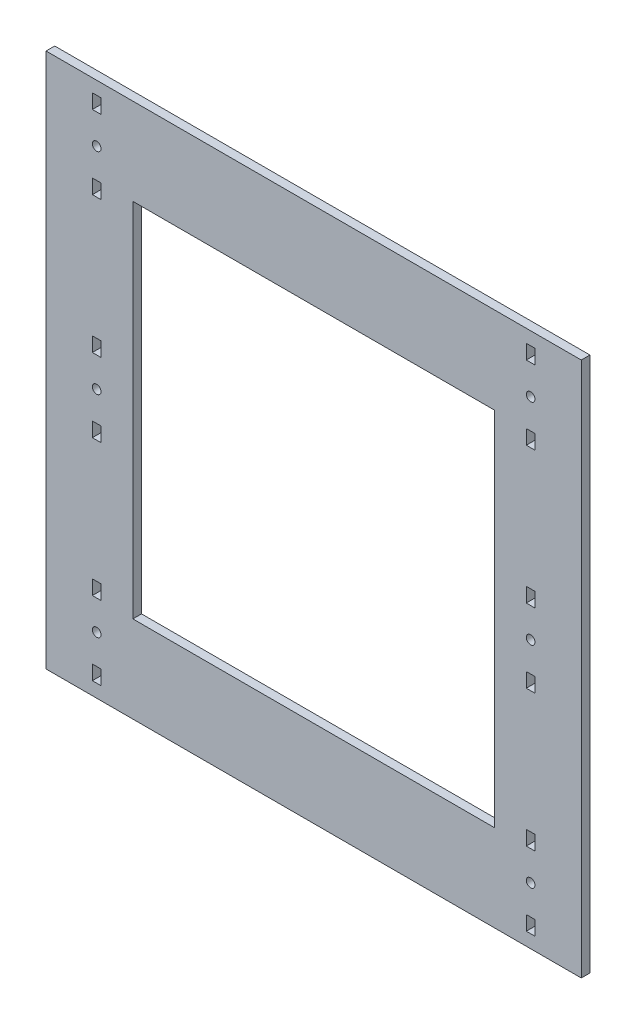
SolidWorks part; units mm, degrees
ref_plane "Front Plane" through (0, 0, 0) normal (0, 0, 1) x (1, 0, 0)
ref_plane "Top Plane" through (0, 0, 0) normal (0, 1, 0) x (1, 0, 0)
ref_plane "Right Plane" through (0, 0, 0) normal (1, 0, 0) x (0, 0, -1)
sketch "Sketch1" plane through (0, 0, 0) normal (0, 0, 1) x (1, 0, 0)
  line L0 (185, 185) -> (-185, -185) construction
  line L1 (-185, 185) -> (185, 185)
  line L2 (-185, 185) -> (-185, -185)
  line L3 (-185, -185) -> (185, -185)
  line L4 (185, 185) -> (185, -185)
  line L5 (-125, 125) -> (125, -125) construction
  line L6 (-125, 125) -> (125, 125)
  line L7 (-125, 125) -> (-125, -125)
  line L8 (-125, -125) -> (125, -125)
  line L9 (125, 125) -> (125, -125)
  line L10 (-150, 185) -> (-150, 176) construction
  line L11 (0, 185) -> (0, -185) construction
  line L12 (-150, 166) -> (-150, 145.5) construction
  line L13 (-153, 176) -> (-147, 176)
  line L14 (-153, 176) -> (-153, 166)
  line L15 (-153, 166) -> (-147, 166)
  line L16 (-147, 176) -> (-147, 166)
  line L17 (-150, 145.5) -> (-150, 125) construction
  line L18 (-150, 115) -> (-150, 30.5) construction
  line L19 (-153, 125) -> (-147, 125)
  line L20 (-153, 125) -> (-153, 115)
  line L21 (-153, 115) -> (-147, 115)
  line L22 (-147, 125) -> (-147, 115)
  line L23 (-150, 0) -> (-150, 20.5) construction
  line L24 (-153, 30.5) -> (-147, 30.5)
  line L25 (-153, 30.5) -> (-153, 20.5)
  line L26 (-153, 20.5) -> (-147, 20.5)
  line L27 (-147, 30.5) -> (-147, 20.5)
  line L28 (-150, 0) -> (-150, -20.5) construction
  line L29 (-150, -30.5) -> (-150, -115) construction
  line L30 (-153, -20.5) -> (-147, -20.5)
  line L31 (-153, -20.5) -> (-153, -30.5)
  line L32 (-153, -30.5) -> (-147, -30.5)
  line L33 (-147, -20.5) -> (-147, -30.5)
  line L34 (-150, -125) -> (-150, -145.5) construction
  line L35 (-153, -115) -> (-147, -115)
  line L36 (-153, -115) -> (-153, -125)
  line L37 (-153, -125) -> (-147, -125)
  line L38 (-147, -115) -> (-147, -125)
  line L39 (-150, -145.5) -> (-150, -166) construction
  line L40 (-150, -176) -> (-150, -185) construction
  line L41 (-153, -166) -> (-147, -166)
  line L42 (-153, -166) -> (-153, -176)
  line L43 (-153, -176) -> (-147, -176)
  line L44 (-147, -166) -> (-147, -176)
  line L45 (153, -176) -> (147, -176)
  line L46 (147, -166) -> (147, -176)
  line L47 (153, -166) -> (147, -166)
  line L48 (153, -166) -> (153, -176)
  line L49 (147, -115) -> (147, -125)
  line L50 (153, -125) -> (147, -125)
  line L51 (153, -115) -> (153, -125)
  line L52 (153, -115) -> (147, -115)
  line L53 (153, -30.5) -> (147, -30.5)
  line L54 (147, -20.5) -> (147, -30.5)
  line L55 (153, -20.5) -> (153, -30.5)
  line L56 (153, -20.5) -> (147, -20.5)
  line L57 (153, 20.5) -> (147, 20.5)
  line L58 (147, 30.5) -> (147, 20.5)
  line L59 (153, 30.5) -> (147, 30.5)
  line L60 (153, 30.5) -> (153, 20.5)
  line L61 (153, 115) -> (147, 115)
  line L62 (147, 125) -> (147, 115)
  line L63 (153, 125) -> (153, 115)
  line L64 (153, 125) -> (147, 125)
  line L65 (147, 176) -> (147, 166)
  line L66 (153, 166) -> (147, 166)
  line L67 (153, 176) -> (147, 176)
  line L68 (153, 176) -> (153, 166)
  circle A0 centre (-150, 145.5) radius 3
  circle A1 centre (-150, 0) radius 3
  circle A2 centre (-150, -145.5) radius 3
  circle A3 centre (150, -145.5) radius 3
  circle A4 centre (150, 0) radius 3
  circle A5 centre (150, 145.5) radius 3
  point P27 (-147, -171)
  point P58 (147, -171)
  dimension "D3" = 6
  dimension "D5" = 6
  dimension "D1" = 370
  dimension "D2" = 250
  dimension "D4" = 10
  dimension "D6" = 9
  dimension "D7" = 41
  dimension "D8" = 35
extrude "Boss-Extrude1" add sketch "Sketch1" along normal mid plane 6
